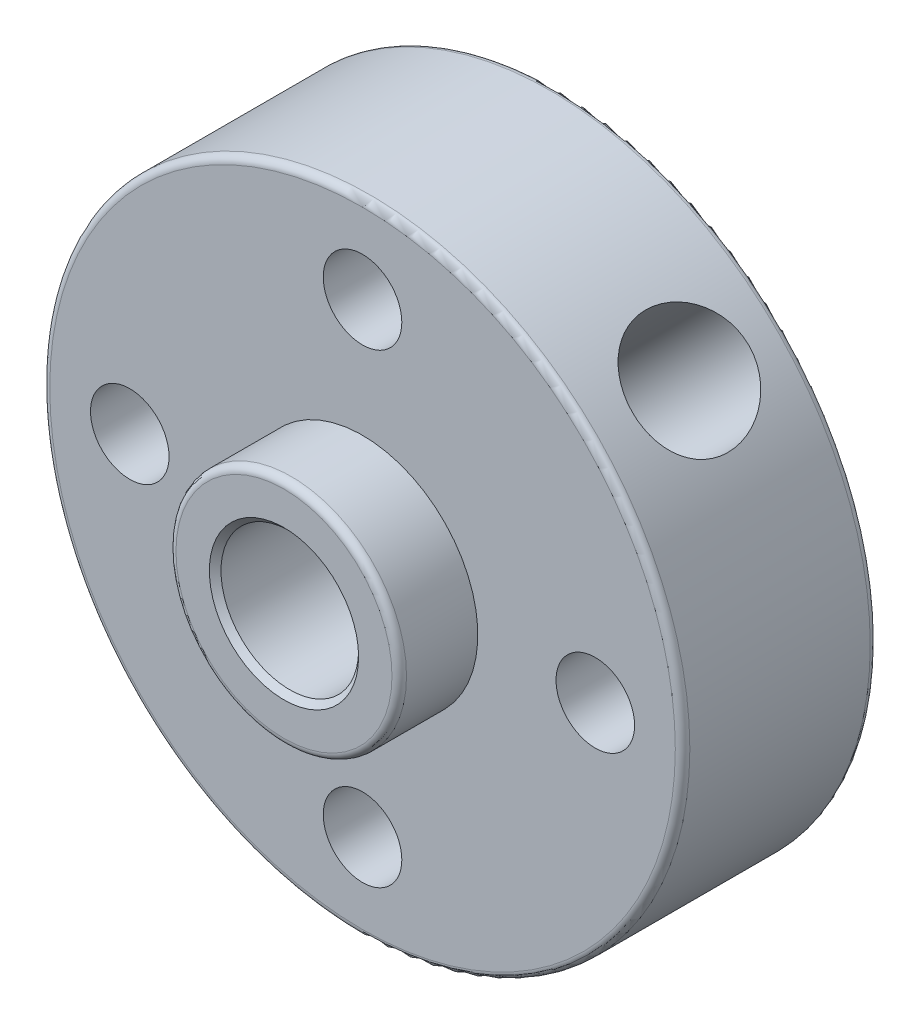
SolidWorks part; units mm, degrees
ref_plane "Front Plane" through (0, 0, 0) normal (0, 0, 1) x (1, 0, 0)
ref_plane "Top Plane" through (0, 0, 0) normal (0, 1, 0) x (1, 0, 0)
ref_plane "Right Plane" through (0, 0, 0) normal (1, 0, 0) x (0, 0, -1)
sketch "Sketch1" plane through (0, 0, 0) normal (0, 0, 1) x (1, 0, 0)
  circle A0 centre (0, 0) radius 11
  dimension "D1" = 22
extrude "Boss-Extrude1" add sketch "Sketch1" against normal blind 6.7
sketch "Sketch2" plane through (0, 0, 0) normal (0, 0, 1) x (1, 0, 0)
  circle A0 centre (0, 0) radius 3.9625
  dimension "D1" = 7.925
extrude "Boss-Extrude2" add sketch "Sketch2" along normal blind 2.7
sketch "Sketch3" plane through (0, 0, 2.7) normal (0, 0, 1) x (1, 0, 0)
  circle A0 centre (0, 0) radius 2.365
  dimension "D1" = 4.73
extrude "Cut-Extrude1" cut sketch "Sketch3" against normal through all
sketch "Sketch4" plane through (0, 0, 0) normal (0, 0, 1) x (1, 0, 0)
  circle A0 centre (0, 0) radius 8 construction
  circle A1 centre (0, 8) radius 1.35
  circle A2 centre (8, 0) radius 1.35
  circle A3 centre (0, -8) radius 1.35
  circle A4 centre (-8, 0) radius 1.35
  dimension "D1" = 16
  dimension "D2" = 2.7
  dimension "D3" = 2.7
  dimension "D4" = 2.7
  dimension "D5" = 2.7
extrude "Cut-Extrude2" cut sketch "Sketch4" against normal through all
cosmetic thread "Cosmetic Thread1" parameters "D2"=3.5052
cosmetic thread "Cosmetic Thread2" parameters "D2"=3.5052
cosmetic thread "Cosmetic Thread3" parameters "D2"=3.5052
cosmetic thread "Cosmetic Thread4" parameters "D2"=3.5052
sketch "Sketch5" plane through (0, 0, 0) normal (0, 0, 1) x (1, 0, 0)
  line L0 (0, 0) -> (10.8252, -10.8252) construction
ref_plane "Plane1" through (0, 0, 0) normal (-0.7071, -0.7071, 0) x (0, 0, 1)
sketch "Sketch6" plane through (0, 0, 0) normal (-0.7071, -0.7071, 0) x (0, 0, 1)
  line L0 (-6.7, 11) -> (-6.7, -11) construction
  circle A0 centre (-3.5, 0) radius 2
  dimension "D2" = 4
  dimension "D1" = 3.2
extrude "Cut-Extrude3" cut sketch "Sketch6" against normal through all
cosmetic thread "Cosmetic Thread5" parameters "D2"=4.826
chamfer "Chamfer1" distance 0.2 angle 45 2 edges at (2.365, 0, -6.7) (2.365, 0, 2.7)
fillet "Fillet1" radius 0.25 3 edges at (11, 0, -6.7) (11, 0, 0) (3.9625, 0, 2.7)
